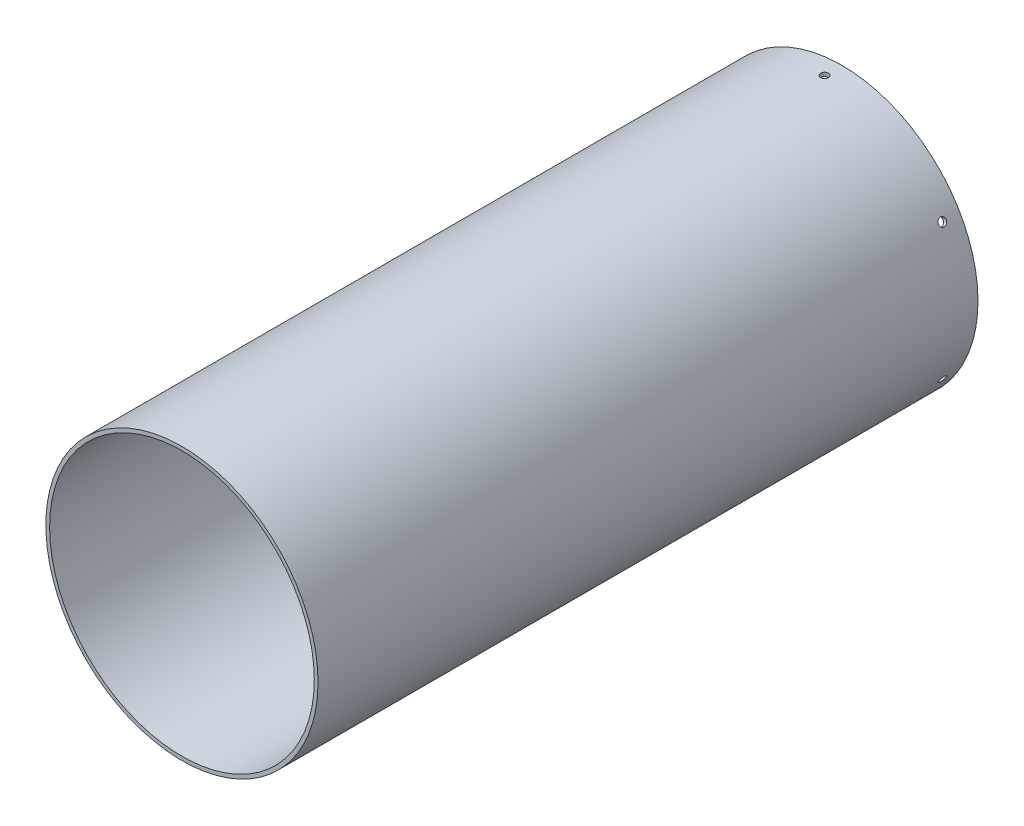
SolidWorks part; units mm, degrees
material "A-Glass Fiber"
ref_plane "Front Plane" through (0, 0, 0) normal (0, 0, 1) x (1, 0, 0)
ref_plane "Top Plane" through (0, 0, 0) normal (0, 1, 0) x (1, 0, 0)
ref_plane "Right Plane" through (0, 0, 0) normal (1, 0, 0) x (0, 0, -1)
sketch "Sketch1" plane through (0, 0, 0) normal (0, 0, 1) x (1, 0, 0)
  circle A0 centre (0, 0) radius 76.2
  circle A1 centre (0, 0) radius 78.359
  dimension "D1" = 156.718
  dimension "D2" = 152.4
extrude "Boss-Extrude1" add sketch "Sketch1" along normal blind 380
sketch "Sketch4" plane through (0, 0, 0) normal (0, 1, 0) x (1, 0, 0)
  line L0 (78.359, 0) -> (-78.359, 0) construction
  point P0 (0, -10)
  dimension "D1" = 10
hole_wizard "M4 Clearance Hole2" positions "Sketch4" profile "Sketch5" hole size "M4" standard "ANSI Metric" end condition through all
sketch "Sketch5" plane through (0, 0, 10) normal (1, 0, 0) x (0, 0, -1)
  line L0 (0, 0) -> (0, 78.359)
  line L1 (0, 78.359) -> (2.25, 78.359)
  line L2 (2.25, 78.359) -> (2.25, 0)
  line L5 (2.25, 0) -> (0, 0)
  line L11 (0, -6.35) -> (0, 107.95) construction
  dimension "Thru Hole Dia." = 4.5
  dimension "Thru Hole Depth" = 78.359
pattern_circular "CirPattern2" count 6 over 360 about axis through (0, 0, 380) along (0, 0, -1) of "M4 Clearance Hole2" reverse direction yes
